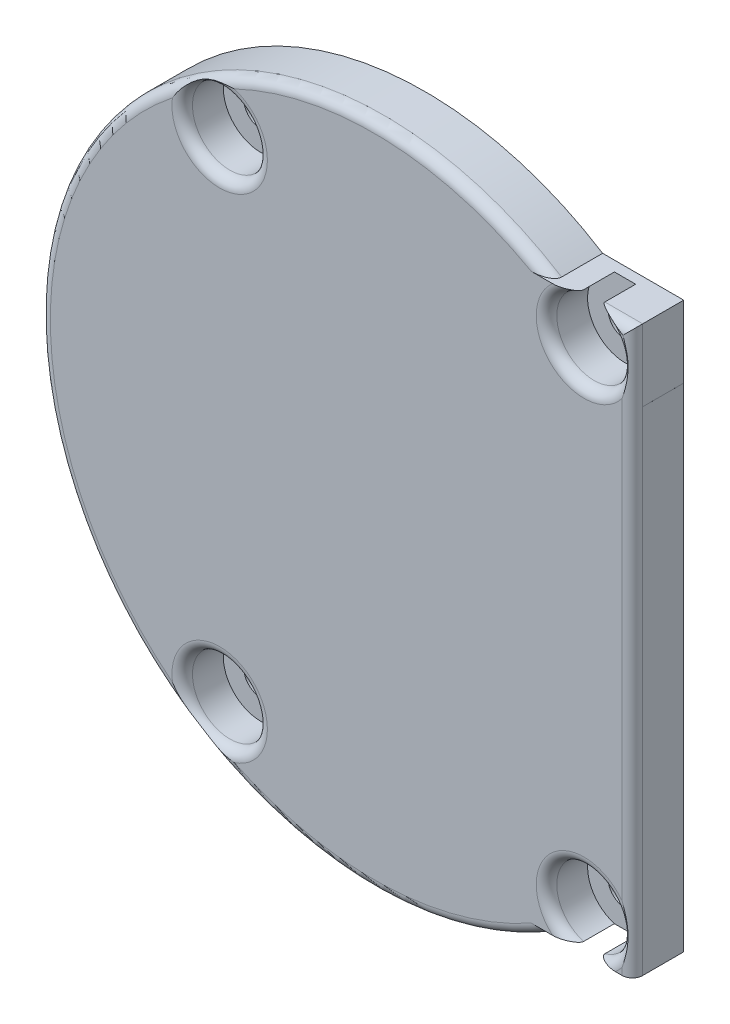
SolidWorks part; units mm, degrees
ref_plane "Ebene vorne" through (0, 0, 0) normal (0, 0, 1) x (1, 0, 0)
ref_plane "Ebene oben" through (0, 0, 0) normal (0, 1, 0) x (1, 0, 0)
ref_plane "Ebene rechts" through (0, 0, 0) normal (1, 0, 0) x (0, 0, -1)
sketch "Skizze1" plane through (0, 0, 0) normal (0, 0, 1) x (1, 0, 0)
  line L0 (30.5, 20.5) -> (30.5, -20.5)
  line L1 (15, -24) -> (-15, -24)
  line L2 (15, -24) -> (15, 24)
  line L3 (15, 24) -> (-15, 24)
  line L4 (-15, -24) -> (-15, 24)
  line L5 (15, -24) -> (-15, 24) construction
  line L6 (15, 24) -> (-15, -24) construction
  line L7 (30.5, -27.5) -> (30.5, 27.5)
  line L8 (30.5, 27.5) -> (30.5, 20.5)
  line L9 (30.5, 24) -> (26.2718, 24) construction
  line L10 (30.5, 27.5) -> (17.3205, 27.5)
  line L11 (30.5, 20.5) -> (25.219, 20.5)
  line L12 (0, 0) -> (8.2887, 0) construction
  line L13 (30.5, 27.5) -> (25.22, 27.5)
  line L14 (30.5, 27.5) -> (30.5, -27.5)
  line L15 (30.5, -27.5) -> (25.22, -27.5)
  line L16 (25.22, 27.5) -> (25.22, -27.5)
  line L17 (30.5, 27.5) -> (25.22, -27.5) construction
  line L18 (30.5, -27.5) -> (25.22, 27.5) construction
  line L19 (25.22, -27.5) -> (17.3205, -27.5)
  circle A0 centre (0, 0) radius 32.5
  circle A1 centre (-15, 24) radius 1.65
  circle A2 centre (20.5, 24) radius 1.65
  circle A3 centre (20.5, -24) radius 1.65
  circle A4 centre (-15, -24) radius 1.65
  point P10 (30.5, 0)
  point P16 (30.5, 0)
  point P22 (27.86, 0)
  dimension "D1" = 65
  dimension "D5" = 3.3
  dimension "D7" = 3.3
  dimension "D2" = 30
  dimension "D3" = 30.5
  dimension "D4" = 41
  dimension "D6" = 10
  dimension "D8" = 55
  dimension "D9" = 5.28
extrude "Aufsatz-Linear austragen1" add sketch "Skizze1" along normal blind 5 contours A0 A3 L16 A2 L1 A4 L4 A1 L3 L2 | L4 A4 L1 L2 L3 A1 | A0 A3 L19 L16 | A2 A0 L11 L16 L10 region at (22.8214, 25.3162, 0) region at (24.3507, 0, 0) region at (22.8214, -25.3162, 0) region at (0.0426, 0, 0)
sketch "Skizze2" plane through (0, 0, 5) normal (0, 0, 1) x (1, 0, 0)
  line L0 (0, 0) -> (4.0673, 0) construction
  circle A0 centre (-15, 24) radius 3.65
  circle A1 centre (20.5, 24) radius 3.65
  circle A2 centre (20.5, -24) radius 3.65
  circle A3 centre (-15, -24) radius 3.65
  dimension "D1" = 7.3
  dimension "D2" = 7.3
extrude "Schnitt-Linear austragen1" cut sketch "Skizze2" against normal blind 4
fillet "Verrundung10" radius 1 7 edges at (20.5, 20.35, 5) (23.3778, 27.5, 5) (25.22, -3.5006, 5) (20.5, -20.35, 5) (-18.65, -24, 5) (-11.35, 24, 5) (-32.5, 0, 5)
